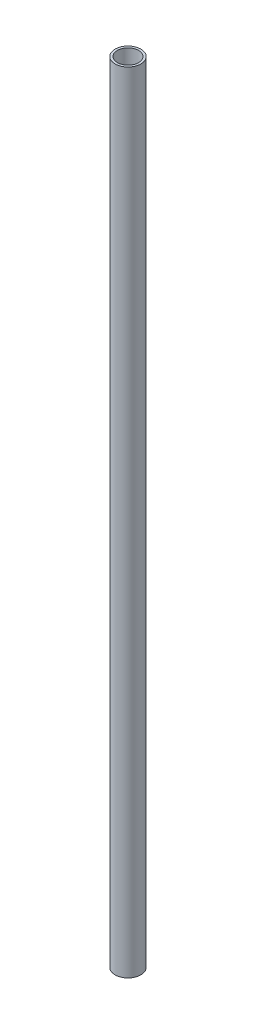
SolidWorks part; units mm, degrees
ref_plane "Front Plane" through (0, 0, 0) normal (0, 0, 1) x (1, 0, 0)
ref_plane "Top Plane" through (0, 0, 0) normal (0, 1, 0) x (1, 0, 0)
ref_plane "Right Plane" through (0, 0, 0) normal (1, 0, 0) x (0, 0, -1)
sketch "Sketch1" plane through (0, 0, 0) normal (0, 1, 0) x (1, 0, 0)
  circle A0 centre (0, 0) radius 17.4625
  circle A1 centre (0, 0) radius 14.4145
  dimension "D1" = 34.925
  dimension "D2" = 28.829
extrude "Boss-Extrude1" add sketch "Sketch1" along normal blind 1070
